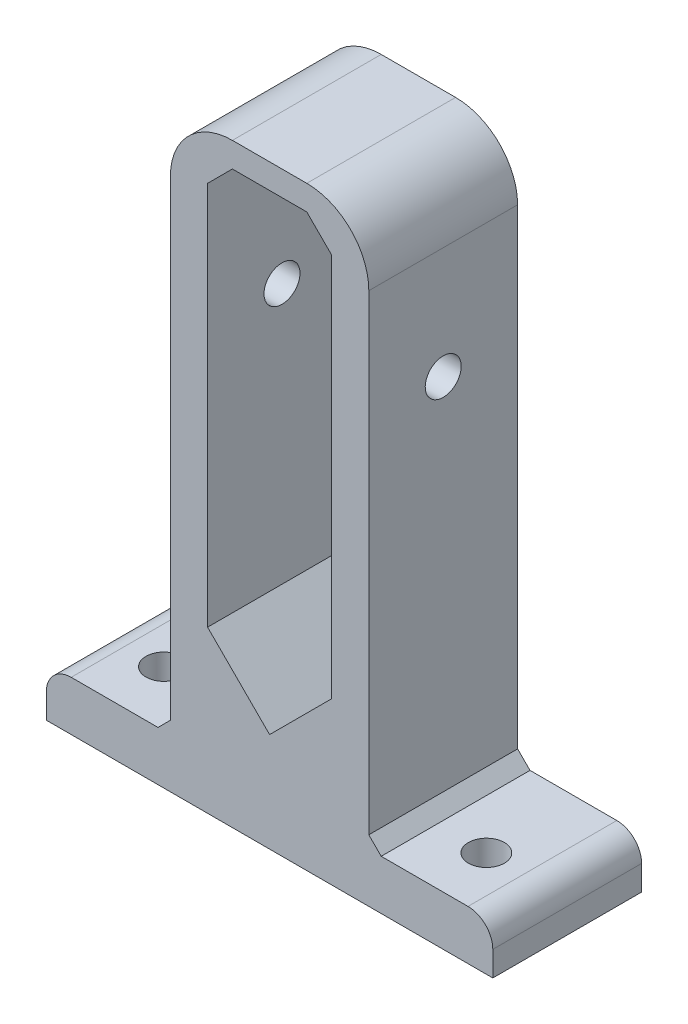
SolidWorks part; units mm, degrees
other "标注1"
sketch "草图5" plane through (0, 46, 0) normal (-0.7504, 0.1083, -0.6521) x (-0.6453, 0.0941, 0.7581)
ref_plane "前视基准面" through (0, 0, 0) normal (0, 0, 1) x (1, 0, 0)
ref_plane "上视基准面" through (0, 0, 0) normal (0, 1, 0) x (1, 0, 0)
ref_plane "右视基准面" through (0, 0, 0) normal (1, 0, 0) x (0, 0, -1)
sketch "草图1" plane through (0, 0, 0) normal (0, 0, 1) x (1, 0, 0)
  line L0 (0, 0) -> (13, 0)
  line L1 (13, 0) -> (13, 46)
  line L2 (13, 46) -> (23, 46)
  line L8 (26, 48) -> (10, 48)
  line L9 (10, 48) -> (10, 4)
  line L10 (10, 4) -> (0, 4)
  line L11 (0, 4) -> (0, 0)
  line L18 (18, 48) -> (18, 46) construction
  line L19 (36, 4) -> (36, 0)
  line L20 (26, 4) -> (36, 4)
  line L21 (26, 48) -> (26, 4)
  line L22 (23, 0) -> (23, 46)
  line L23 (36, 0) -> (23, 0)
  dimension "D1" = 10
  dimension "D2" = 16
  dimension "D3" = 2
  dimension "D4" = 4
  dimension "D6" = 44
  dimension "D9" = 13
extrude "凸台-拉伸1" add sketch "草图1" along normal blind 12
sketch "草图2" plane through (13, 0, 0) normal (1, 0, 0) x (0, 0, -1)
  line L0 (-12, 0) -> (-12, 34) construction
  line L2 (-12, 34) -> (-6, 34) construction
  circle A0 centre (-6, 34) radius 1.45
  dimension "D3" = 2.9
  dimension "D1" = 34
  dimension "D2" = 6
extrude "切除-拉伸1" cut sketch "草图2" against normal blind 15 and the other way blind 15
sketch "草图3" plane through (0, 4, 0) normal (0, 1, 0) x (1, 0, 0)
  line L0 (5, 0) -> (5, -7.5192) construction
  line L1 (10, 0) -> (0, 0) construction
  line L2 (18, 0) -> (18, -3.8379) construction
  line L3 (26, 0) -> (10, 0) construction
  circle A0 centre (5, -7.5192) radius 1.45
  circle A1 centre (31, -7.5192) radius 1.45
  dimension "D1" = 2.9
extrude "切除-拉伸2" cut sketch "草图3" against normal blind 15
fillet "圆角2" radius 5 2 edges at (26, 48, 6) (10, 48, 6)
fillet "圆角3" radius 2 2 edges at (36, 4, 6) (0, 4, 6)
chamfer "倒角1" distance 2 angle 45 2 edges at (13, 46, 6) (23, 46, 6)
sketch "草图4" plane through (13, 0, 0) normal (1, 0, 0) x (0, 0, -1)
  line L0 (0, 4) -> (0, 43) construction
  line L1 (-12, 0) -> (0, 0)
  line L2 (-12, 0) -> (-12, 8)
  line L3 (-12, 8) -> (0, 8)
  line L4 (0, 0) -> (0, 8)
  dimension "D1" = 8
extrude "凸台-拉伸2" add sketch "草图4" along normal blind 10
chamfer "倒角2" distance 5 angle 45 2 edges at (13, 8, 6) (23, 8, 6)
chamfer "倒角3" distance 1 angle 45 2 edges at (26, 4, 6) (10, 4, 6)
